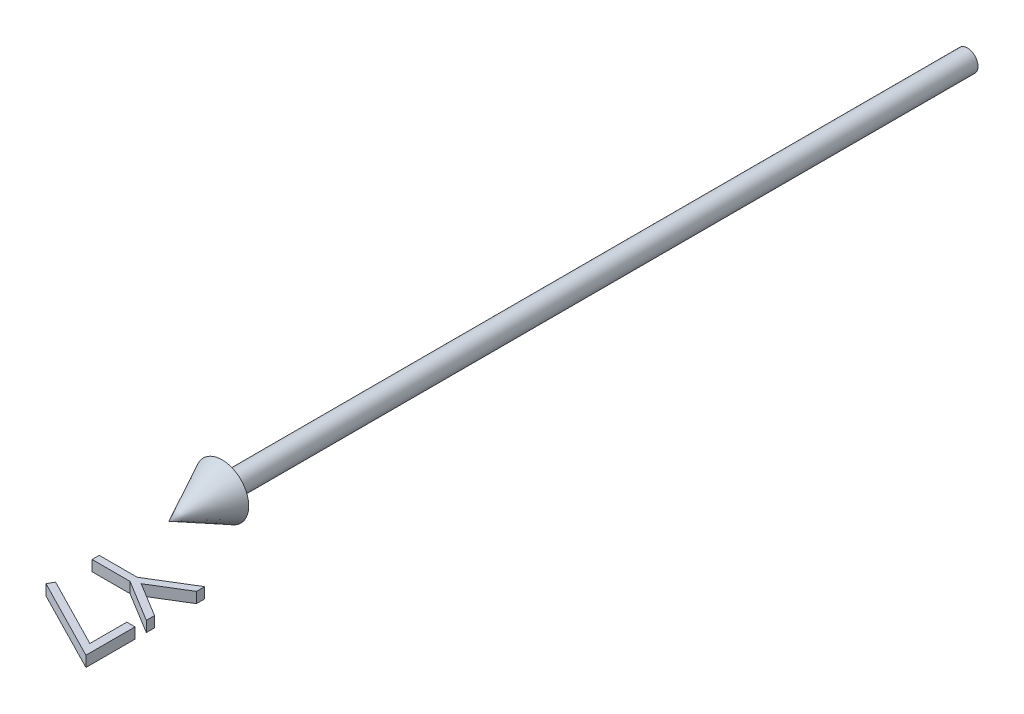
SolidWorks part; units mm, degrees
ref_plane "Front Plane" through (0, 0, 0) normal (0, 0, 1) x (1, 0, 0)
ref_plane "Top Plane" through (0, 0, 0) normal (0, 1, 0) x (1, 0, 0)
ref_plane "Right Plane" through (0, 0, 0) normal (1, 0, 0) x (0, 0, -1)
sketch "Sketch2" plane through (0, 0, 0) normal (0, 1, 0) x (1, 0, 0)
  line L0 (0, 41.95) -> (0, -114.4521) construction
  line L1 (-36.8894, 0) -> (41.4965, 0) construction
  line L2 (0, -150) -> (5, -140)
  line L3 (5, -140) -> (2, -140)
  line L4 (2, -140) -> (2, 0)
  line L5 (2, 0) -> (0, 0)
  line L6 (0, 0) -> (0, -150)
  dimension "D1" = 150
  dimension "D2" = 2
  dimension "D3" = 10
  dimension "D4" = 5
revolve "Revolve1" add sketch "Sketch2" angle 360 about L0
sketch "Sketch3" plane through (0, 0, 0) normal (0, 1, 0) x (1, 0, 0)
  line L0 (0, -157.5) -> (0, -263.6294) construction
  line L1 (-28.6061, 0) -> (32.6573, 0) construction
  text T0 "Y7\r\n\r\n\r\n" font "Century Gothic" height 15
  point P6 (0, -163.1078)
  point P7 (0, -182.4469)
  point P8 (0, -154.8359)
  point P9 (0, -200.5829)
  point P10 (0, -263.6294)
  dimension "D1" = 157.5
extrude "Boss-Extrude1" add sketch "Sketch3" against normal blind 1 and the other way blind 1 separate body
equation "\"D1@Sketch2\"=\"frame_arrow_length\""
equation "\"D2@Sketch2\"=\"frame_arrow_odA\"/2"
equation "\"D4@Sketch2\"=\"frame_arrow_head_od\""
equation "\"D3@Sketch2\"=\"frame_arrow_head_length\""
equation "\"frame_arrow_length\"=150"
equation "\"frame_arrow_head_length\"=10"
equation "\"frame_arrow_head_od\"=5"
equation "\"frame_arrow_odA\"=4"
equation "\"D1@Sketch3\"=\"frame_arrow_length\"*1.05"
